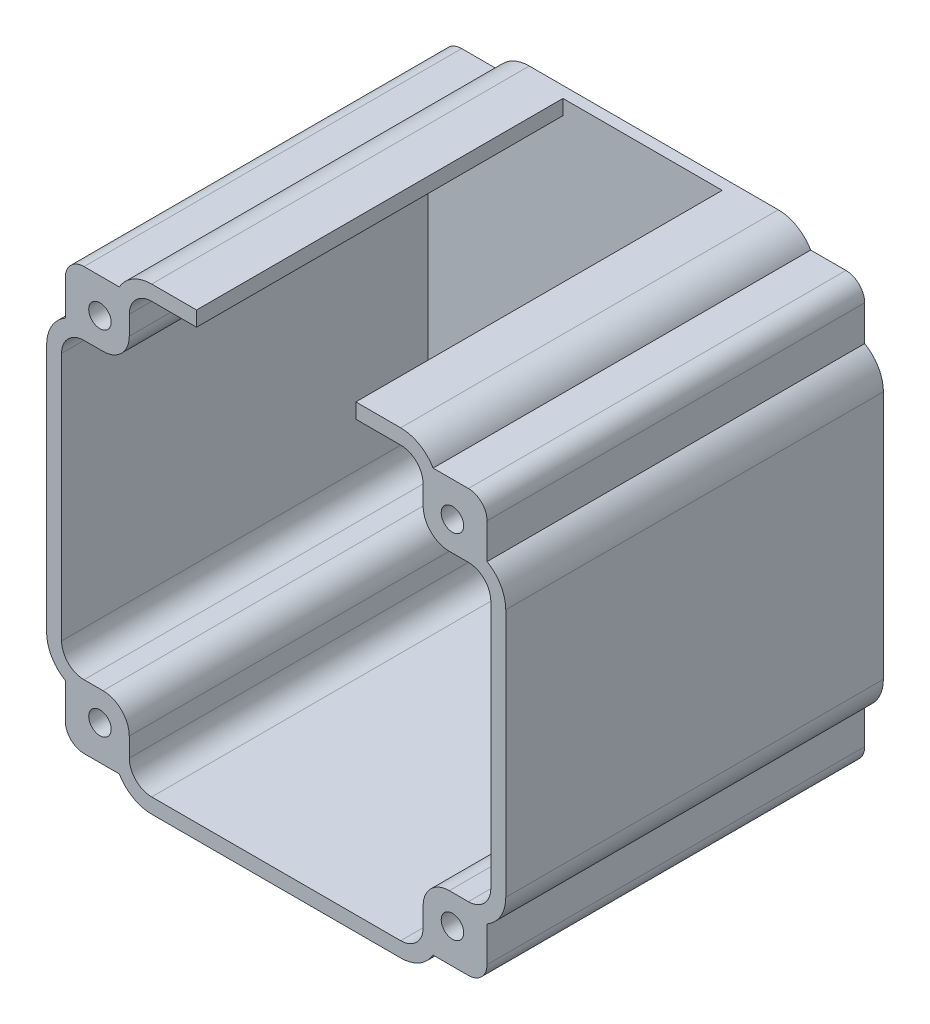
SolidWorks part; units mm, degrees
ref_plane "Front Plane" through (0, 0, 0) normal (0, 0, 1) x (1, 0, 0)
ref_plane "Top Plane" through (0, 0, 0) normal (0, 1, 0) x (1, 0, 0)
ref_plane "Right Plane" through (0, 0, 0) normal (1, 0, 0) x (0, 0, -1)
sketch "Sketch1" plane through (0, 0, -54) normal (0, 0, -1) x (-1, 0, 0)
  line L0 (-25.7, -19.65) -> (-23.15, -19.65)
  line L1 (-19.65, -23.15) -> (-19.65, -25.7)
  line L2 (-16.65, -28.7) -> (16.65, -28.7)
  line L3 (19.65, -25.7) -> (19.65, -23.15)
  line L4 (23.15, -19.65) -> (25.7, -19.65)
  line L5 (28.7, -16.65) -> (28.7, 16.65)
  line L6 (25.7, 19.65) -> (23.15, 19.65)
  line L7 (19.65, 23.15) -> (19.65, 25.7)
  line L8 (16.65, 28.7) -> (10.65, 28.7)
  line L9 (-19.65, 25.7) -> (-19.65, 23.15)
  line L10 (-23.15, 19.65) -> (-25.7, 19.65)
  line L11 (-28.7, 16.65) -> (-28.7, -16.65)
  line L12 (-25.7, -18.65) -> (-23.15, -18.65)
  line L13 (-18.65, -23.15) -> (-18.65, -25.7)
  line L14 (-16.65, -27.7) -> (16.65, -27.7)
  line L15 (18.65, -25.7) -> (18.65, -23.15)
  line L16 (23.15, -18.65) -> (25.7, -18.65)
  line L17 (27.7, -16.65) -> (27.7, 16.65)
  line L18 (25.7, 18.65) -> (23.15, 18.65)
  line L19 (18.65, 23.15) -> (18.65, 25.7)
  line L20 (16.65, 27.7) -> (-16.65, 27.7)
  line L21 (-18.65, 25.7) -> (-18.65, 23.15)
  line L22 (-23.15, 18.65) -> (-25.7, 18.65)
  line L23 (-27.7, 16.65) -> (-27.7, -16.65)
  line L24 (-25.7, -18.65) -> (-23.15, -18.65) construction
  line L25 (-18.65, -23.15) -> (-18.65, -25.7) construction
  line L26 (-16.65, -27.7) -> (16.65, -27.7) construction
  line L27 (18.65, -25.7) -> (18.65, -23.15) construction
  line L28 (23.15, -18.65) -> (25.7, -18.65) construction
  line L29 (27.7, -16.65) -> (27.7, 16.65) construction
  line L30 (25.7, 18.65) -> (23.15, 18.65) construction
  line L31 (18.65, 23.15) -> (18.65, 25.7) construction
  line L32 (16.65, 27.7) -> (-16.65, 27.7) construction
  line L33 (-18.65, 25.7) -> (-18.65, 23.15) construction
  line L34 (-23.15, 18.65) -> (-25.7, 18.65) construction
  line L35 (-27.7, 16.65) -> (-27.7, -16.65) construction
  line L36 (-25.7, -21.65) -> (-23.15, -21.65)
  line L37 (-21.65, -23.15) -> (-21.65, -25.7)
  line L38 (-16.65, -30.7) -> (16.65, -30.7)
  line L39 (21.65, -25.7) -> (21.65, -23.15)
  line L40 (23.15, -21.65) -> (25.7, -21.65)
  line L41 (30.7, -16.65) -> (30.7, 16.65)
  line L42 (25.7, 21.65) -> (23.15, 21.65)
  line L43 (21.65, 23.15) -> (21.65, 25.7)
  line L44 (16.65, 30.7) -> (10.65, 30.7)
  line L45 (-21.65, 25.7) -> (-21.65, 23.15)
  line L46 (-23.15, 21.65) -> (-25.7, 21.65)
  line L47 (-30.7, 16.65) -> (-30.7, -16.65)
  line L48 (-10.65, 30.7) -> (-10.65, 28.7)
  line L49 (10.65, 30.7) -> (10.65, 28.7)
  line L50 (-10.65, 30.7) -> (-16.65, 30.7)
  line L51 (16.65, 30.7) -> (-16.65, 30.7) construction
  line L52 (-10.65, 28.7) -> (-16.65, 28.7)
  line L53 (16.65, 28.7) -> (-16.65, 28.7) construction
  arc A0 (-19.65, -23.15) -> (-23.15, -19.65) centre (-23.15, -23.15) ccw
  arc A1 (-19.65, -25.7) -> (-16.65, -28.7) centre (-16.65, -25.7) ccw
  arc A2 (16.65, -28.7) -> (19.65, -25.7) centre (16.65, -25.7) ccw
  arc A3 (23.15, -19.65) -> (19.65, -23.15) centre (23.15, -23.15) ccw
  arc A4 (25.7, -19.65) -> (28.7, -16.65) centre (25.7, -16.65) ccw
  arc A5 (28.7, 16.65) -> (25.7, 19.65) centre (25.7, 16.65) ccw
  arc A6 (19.65, 23.15) -> (23.15, 19.65) centre (23.15, 23.15) ccw
  arc A7 (19.65, 25.7) -> (16.65, 28.7) centre (16.65, 25.7) ccw
  arc A8 (-16.65, 28.7) -> (-19.65, 25.7) centre (-16.65, 25.7) ccw
  arc A9 (-23.15, 19.65) -> (-19.65, 23.15) centre (-23.15, 23.15) ccw
  arc A10 (-25.7, 19.65) -> (-28.7, 16.65) centre (-25.7, 16.65) ccw
  arc A11 (-28.7, -16.65) -> (-25.7, -19.65) centre (-25.7, -16.65) ccw
  arc A12 (-27.7, -16.65) -> (-25.7, -18.65) centre (-25.7, -16.65) ccw
  arc A13 (-18.65, -23.15) -> (-23.15, -18.65) centre (-23.15, -23.15) ccw
  arc A14 (-18.65, -25.7) -> (-16.65, -27.7) centre (-16.65, -25.7) ccw
  arc A15 (16.65, -27.7) -> (18.65, -25.7) centre (16.65, -25.7) ccw
  arc A16 (23.15, -18.65) -> (18.65, -23.15) centre (23.15, -23.15) ccw
  arc A17 (25.7, -18.65) -> (27.7, -16.65) centre (25.7, -16.65) ccw
  arc A18 (27.7, 16.65) -> (25.7, 18.65) centre (25.7, 16.65) ccw
  arc A19 (18.65, 23.15) -> (23.15, 18.65) centre (23.15, 23.15) ccw
  arc A20 (18.65, 25.7) -> (16.65, 27.7) centre (16.65, 25.7) ccw
  arc A21 (-16.65, 27.7) -> (-18.65, 25.7) centre (-16.65, 25.7) ccw
  arc A22 (-23.15, 18.65) -> (-18.65, 23.15) centre (-23.15, 23.15) ccw
  arc A23 (-25.7, 18.65) -> (-27.7, 16.65) centre (-25.7, 16.65) ccw
  arc A24 (-27.7, -16.65) -> (-25.7, -18.65) centre (-25.7, -16.65) ccw construction
  arc A25 (-18.65, -23.15) -> (-23.15, -18.65) centre (-23.15, -23.15) ccw construction
  arc A26 (-18.65, -25.7) -> (-16.65, -27.7) centre (-16.65, -25.7) ccw construction
  arc A27 (16.65, -27.7) -> (18.65, -25.7) centre (16.65, -25.7) ccw construction
  arc A28 (23.15, -18.65) -> (18.65, -23.15) centre (23.15, -23.15) ccw construction
  arc A29 (25.7, -18.65) -> (27.7, -16.65) centre (25.7, -16.65) ccw construction
  arc A30 (27.7, 16.65) -> (25.7, 18.65) centre (25.7, 16.65) ccw construction
  arc A31 (18.65, 23.15) -> (23.15, 18.65) centre (23.15, 23.15) ccw construction
  arc A32 (18.65, 25.7) -> (16.65, 27.7) centre (16.65, 25.7) ccw construction
  arc A33 (-16.65, 27.7) -> (-18.65, 25.7) centre (-16.65, 25.7) ccw construction
  arc A34 (-23.15, 18.65) -> (-18.65, 23.15) centre (-23.15, 23.15) ccw construction
  arc A35 (-25.7, 18.65) -> (-27.7, 16.65) centre (-25.7, 16.65) ccw construction
  arc A36 (-21.65, -23.15) -> (-23.15, -21.65) centre (-23.15, -23.15) ccw
  arc A37 (-21.65, -25.7) -> (-16.65, -30.7) centre (-16.65, -25.7) ccw
  arc A38 (16.65, -30.7) -> (21.65, -25.7) centre (16.65, -25.7) ccw
  arc A39 (23.15, -21.65) -> (21.65, -23.15) centre (23.15, -23.15) ccw
  arc A40 (25.7, -21.65) -> (30.7, -16.65) centre (25.7, -16.65) ccw
  arc A41 (30.7, 16.65) -> (25.7, 21.65) centre (25.7, 16.65) ccw
  arc A42 (21.65, 23.15) -> (23.15, 21.65) centre (23.15, 23.15) ccw
  arc A43 (21.65, 25.7) -> (16.65, 30.7) centre (16.65, 25.7) ccw
  arc A44 (-16.65, 30.7) -> (-21.65, 25.7) centre (-16.65, 25.7) ccw
  arc A45 (-23.15, 21.65) -> (-21.65, 23.15) centre (-23.15, 23.15) ccw
  arc A46 (-25.7, 21.65) -> (-30.7, 16.65) centre (-25.7, 16.65) ccw
  arc A47 (-30.7, -16.65) -> (-25.7, -21.65) centre (-25.7, -16.65) ccw
  dimension "D4" = 6
  dimension "D5" = 6
  dimension "D1" = 0
  dimension "D2" = 1
  dimension "D3" = 2
extrude "Boss-Extrude1" add sketch "Sketch1" against normal up to surface (49 mm away)
sketch "Sketch2" plane through (0, 0, -54) normal (0, 0, -1) x (-1, 0, 0)
  line L0 (-10.65, 30.7) -> (10.65, 30.7)
  line L12 (-25.7, -21.65) -> (-23.15, -21.65)
  line L13 (-21.65, -23.15) -> (-21.65, -25.7)
  line L14 (-16.65, -30.7) -> (16.65, -30.7)
  line L15 (21.65, -25.7) -> (21.65, -23.15)
  line L16 (23.15, -21.65) -> (25.7, -21.65)
  line L17 (30.7, -16.65) -> (30.7, 16.65)
  line L18 (25.7, 21.65) -> (23.15, 21.65)
  line L19 (21.65, 23.15) -> (21.65, 25.7)
  line L20 (16.65, 30.7) -> (10.65, 30.7)
  line L21 (-21.65, 25.7) -> (-21.65, 23.15)
  line L22 (-23.15, 21.65) -> (-25.7, 21.65)
  line L23 (-30.7, 16.65) -> (-30.7, -16.65)
  line L24 (-25.7, -21.65) -> (-23.15, -21.65)
  line L25 (-21.65, -23.15) -> (-21.65, -25.7)
  line L26 (-16.65, -30.7) -> (16.65, -30.7)
  line L27 (21.65, -25.7) -> (21.65, -23.15)
  line L28 (23.15, -21.65) -> (25.7, -21.65)
  line L29 (30.7, -16.65) -> (30.7, 16.65)
  line L30 (25.7, 21.65) -> (23.15, 21.65)
  line L31 (21.65, 23.15) -> (21.65, 25.7)
  line L32 (16.65, 30.7) -> (10.65, 30.7)
  line L33 (-21.65, 25.7) -> (-21.65, 23.15)
  line L34 (-23.15, 21.65) -> (-25.7, 21.65)
  line L35 (-30.7, 16.65) -> (-30.7, -16.65)
  line L52 (-28.7, -16.65) -> (-28.7, 16.65)
  line L54 (-25.7, 19.65) -> (-23.15, 19.65)
  line L56 (-19.65, 23.15) -> (-19.65, 25.7)
  line L58 (-16.65, 28.7) -> (-10.65, 28.7)
  line L60 (-10.65, 28.7) -> (-10.65, 30.7)
  line L62 (-10.65, 30.7) -> (-16.65, 30.7)
  line L63 (-10.65, 30.7) -> (-16.65, 30.7)
  line L64 (10.65, 30.7) -> (10.65, 28.7)
  line L66 (10.65, 28.7) -> (16.65, 28.7)
  line L68 (19.65, 25.7) -> (19.65, 23.15)
  line L70 (23.15, 19.65) -> (25.7, 19.65)
  line L72 (28.7, 16.65) -> (28.7, -16.65)
  line L74 (25.7, -19.65) -> (23.15, -19.65)
  line L76 (19.65, -23.15) -> (19.65, -25.7)
  line L78 (16.65, -28.7) -> (-16.65, -28.7)
  line L80 (-19.65, -25.7) -> (-19.65, -23.15)
  line L82 (-23.15, -19.65) -> (-25.7, -19.65)
  arc A12 (-30.7, -16.65) -> (-25.7, -21.65) centre (-25.7, -16.65) ccw
  arc A13 (-21.65, -23.15) -> (-23.15, -21.65) centre (-23.15, -23.15) ccw
  arc A14 (-21.65, -25.7) -> (-16.65, -30.7) centre (-16.65, -25.7) ccw
  arc A15 (16.65, -30.7) -> (21.65, -25.7) centre (16.65, -25.7) ccw
  arc A16 (23.15, -21.65) -> (21.65, -23.15) centre (23.15, -23.15) ccw
  arc A17 (25.7, -21.65) -> (30.7, -16.65) centre (25.7, -16.65) ccw
  arc A18 (30.7, 16.65) -> (25.7, 21.65) centre (25.7, 16.65) ccw
  arc A19 (21.65, 23.15) -> (23.15, 21.65) centre (23.15, 23.15) ccw
  arc A20 (21.65, 25.7) -> (16.65, 30.7) centre (16.65, 25.7) ccw
  arc A21 (-16.65, 30.7) -> (-21.65, 25.7) centre (-16.65, 25.7) ccw
  arc A22 (-23.15, 21.65) -> (-21.65, 23.15) centre (-23.15, 23.15) ccw
  arc A23 (-25.7, 21.65) -> (-30.7, 16.65) centre (-25.7, 16.65) ccw
  arc A24 (-30.7, -16.65) -> (-25.7, -21.65) centre (-25.7, -16.65) ccw
  arc A25 (-21.65, -23.15) -> (-23.15, -21.65) centre (-23.15, -23.15) ccw
  arc A26 (-21.65, -25.7) -> (-16.65, -30.7) centre (-16.65, -25.7) ccw
  arc A27 (16.65, -30.7) -> (21.65, -25.7) centre (16.65, -25.7) ccw
  arc A28 (23.15, -21.65) -> (21.65, -23.15) centre (23.15, -23.15) ccw
  arc A29 (25.7, -21.65) -> (30.7, -16.65) centre (25.7, -16.65) ccw
  arc A30 (30.7, 16.65) -> (25.7, 21.65) centre (25.7, 16.65) ccw
  arc A31 (21.65, 23.15) -> (23.15, 21.65) centre (23.15, 23.15) ccw
  arc A32 (21.65, 25.7) -> (16.65, 30.7) centre (16.65, 25.7) ccw
  arc A33 (-16.65, 30.7) -> (-21.65, 25.7) centre (-16.65, 25.7) ccw
  arc A34 (-23.15, 21.65) -> (-21.65, 23.15) centre (-23.15, 23.15) ccw
  arc A35 (-25.7, 21.65) -> (-30.7, 16.65) centre (-25.7, 16.65) ccw
  arc A48 (-28.7, -16.65) -> (-25.7, -19.65) centre (-25.7, -16.65) ccw
  arc A50 (-25.7, 19.65) -> (-28.7, 16.65) centre (-25.7, 16.65) ccw
  arc A52 (-23.15, 19.65) -> (-19.65, 23.15) centre (-23.15, 23.15) ccw
  arc A54 (-16.65, 28.7) -> (-19.65, 25.7) centre (-16.65, 25.7) ccw
  arc A56 (19.65, 25.7) -> (16.65, 28.7) centre (16.65, 25.7) ccw
  arc A58 (19.65, 23.15) -> (23.15, 19.65) centre (23.15, 23.15) ccw
  arc A60 (28.7, 16.65) -> (25.7, 19.65) centre (25.7, 16.65) ccw
  arc A62 (25.7, -19.65) -> (28.7, -16.65) centre (25.7, -16.65) ccw
  arc A64 (23.15, -19.65) -> (19.65, -23.15) centre (23.15, -23.15) ccw
  arc A66 (16.65, -28.7) -> (19.65, -25.7) centre (16.65, -25.7) ccw
  arc A68 (-19.65, -25.7) -> (-16.65, -28.7) centre (-16.65, -25.7) ccw
  arc A70 (-19.65, -23.15) -> (-23.15, -19.65) centre (-23.15, -23.15) ccw
  dimension "D1" = 0
extrude "Boss-Extrude2" add sketch "Sketch2" along normal blind 1.5
sketch "Sketch3" plane through (0, 0, -55.5) normal (0, 0, -1) x (-1, 0, 0)
  line L0 (-21.65, 25.7) -> (-21.65, 23.15) construction
  line L1 (-25.7, 28.2) -> (-20.9801, 28.2) construction
  line L2 (-28.2, 20.9801) -> (-28.2, 25.7) construction
  line L3 (-23.15, 21.65) -> (-25.7, 21.65) construction
  line L4 (21.65, 25.7) -> (21.65, 23.15)
  line L5 (25.7, 28.2) -> (20.9801, 28.2)
  line L6 (28.2, 20.9801) -> (28.2, 25.7)
  line L7 (23.15, 21.65) -> (25.7, 21.65)
  line L8 (21.65, 25.7) -> (21.65, 23.15)
  line L9 (25.7, 28.2) -> (20.9801, 28.2)
  line L10 (28.2, 20.9801) -> (28.2, 25.7)
  line L11 (23.15, 21.65) -> (25.7, 21.65)
  line L12 (-23.15, -21.65) -> (-25.7, -21.65)
  line L13 (-21.65, -25.7) -> (-21.65, -23.15)
  line L14 (-25.7, -28.2) -> (-20.9801, -28.2)
  line L15 (-28.2, -20.9801) -> (-28.2, -25.7)
  line L16 (-23.15, -21.65) -> (-25.7, -21.65)
  line L17 (-21.65, -25.7) -> (-21.65, -23.15)
  line L18 (-25.7, -28.2) -> (-20.9801, -28.2)
  line L19 (-28.2, -20.9801) -> (-28.2, -25.7)
  line L20 (25.7, -21.65) -> (23.15, -21.65)
  line L21 (21.65, -23.15) -> (21.65, -25.7)
  line L22 (20.9801, -28.2) -> (25.7, -28.2)
  line L23 (28.2, -25.7) -> (28.2, -20.9801)
  line L24 (25.7, -21.65) -> (23.15, -21.65)
  line L25 (21.65, -23.15) -> (21.65, -25.7)
  line L26 (20.9801, -28.2) -> (25.7, -28.2)
  line L27 (28.2, -25.7) -> (28.2, -20.9801)
  line L28 (-21.65, 25.7) -> (-21.65, 23.15)
  line L29 (-25.7, 28.2) -> (-20.9801, 28.2)
  line L30 (-28.2, 20.9801) -> (-28.2, 25.7)
  line L31 (-23.15, 21.65) -> (-25.7, 21.65)
  arc A0 (-20.9801, 28.2) -> (-21.65, 25.7) centre (-16.65, 25.7) ccw construction
  arc A1 (-25.7, 28.2) -> (-28.2, 25.7) centre (-25.7, 25.7) ccw construction
  arc A2 (-25.7, 21.65) -> (-28.2, 20.9801) centre (-25.7, 16.65) ccw construction
  arc A3 (-20.9801, 28.2) -> (-21.65, 25.7) centre (-16.65, 25.7) ccw
  arc A4 (21.65, 25.7) -> (20.9801, 28.2) centre (16.65, 25.7) ccw
  arc A5 (28.2, 25.7) -> (25.7, 28.2) centre (25.7, 25.7) ccw
  arc A6 (28.2, 20.9801) -> (25.7, 21.65) centre (25.7, 16.65) ccw
  arc A7 (21.65, 23.15) -> (23.15, 21.65) centre (23.15, 23.15) ccw
  arc A8 (21.65, 25.7) -> (20.9801, 28.2) centre (16.65, 25.7) ccw
  arc A9 (28.2, 25.7) -> (25.7, 28.2) centre (25.7, 25.7) ccw
  arc A10 (28.2, 20.9801) -> (25.7, 21.65) centre (25.7, 16.65) ccw
  arc A11 (21.65, 23.15) -> (23.15, 21.65) centre (23.15, 23.15) ccw
  arc A12 (-21.65, -23.15) -> (-23.15, -21.65) centre (-23.15, -23.15) ccw
  arc A13 (-21.65, -25.7) -> (-20.9801, -28.2) centre (-16.65, -25.7) ccw
  arc A14 (-28.2, -25.7) -> (-25.7, -28.2) centre (-25.7, -25.7) ccw
  arc A15 (-28.2, -20.9801) -> (-25.7, -21.65) centre (-25.7, -16.65) ccw
  arc A16 (-21.65, -23.15) -> (-23.15, -21.65) centre (-23.15, -23.15) ccw
  arc A17 (-21.65, -25.7) -> (-20.9801, -28.2) centre (-16.65, -25.7) ccw
  arc A18 (-28.2, -25.7) -> (-25.7, -28.2) centre (-25.7, -25.7) ccw
  arc A19 (-28.2, -20.9801) -> (-25.7, -21.65) centre (-25.7, -16.65) ccw
  arc A20 (23.15, -21.65) -> (21.65, -23.15) centre (23.15, -23.15) ccw
  arc A21 (20.9801, -28.2) -> (21.65, -25.7) centre (16.65, -25.7) ccw
  arc A22 (25.7, -28.2) -> (28.2, -25.7) centre (25.7, -25.7) ccw
  arc A23 (25.7, -21.65) -> (28.2, -20.9801) centre (25.7, -16.65) ccw
  arc A24 (23.15, -21.65) -> (21.65, -23.15) centre (23.15, -23.15) ccw
  arc A25 (20.9801, -28.2) -> (21.65, -25.7) centre (16.65, -25.7) ccw
  arc A26 (25.7, -28.2) -> (28.2, -25.7) centre (25.7, -25.7) ccw
  arc A27 (25.7, -21.65) -> (28.2, -20.9801) centre (25.7, -16.65) ccw
  arc A28 (-25.7, 28.2) -> (-28.2, 25.7) centre (-25.7, 25.7) ccw
  arc A29 (-25.7, 21.65) -> (-28.2, 20.9801) centre (-25.7, 16.65) ccw
  point P47 (0, 0)
  arc M25 (-30.7, -16.65) -> (-25.7, -21.65) centre (-25.7, -16.65) ccw
  line M26 (-25.7, -21.65) -> (-23.15, -21.65)
  arc M27 (-23.15, -21.65) -> (-21.65, -23.15) centre (-23.15, -23.15) cw
  line M28 (-21.65, -23.15) -> (-21.65, -25.7)
  arc M29 (-21.65, -25.7) -> (-16.65, -30.7) centre (-16.65, -25.7) ccw
  arc M31 (16.65, -30.7) -> (21.65, -25.7) centre (16.65, -25.7) ccw
  line M32 (21.65, -25.7) -> (21.65, -23.15)
  arc M33 (21.65, -23.15) -> (23.15, -21.65) centre (23.15, -23.15) cw
  line M34 (23.15, -21.65) -> (25.7, -21.65)
  arc M35 (25.7, -21.65) -> (30.7, -16.65) centre (25.7, -16.65) ccw
  arc M37 (30.7, 16.65) -> (25.7, 21.65) centre (25.7, 16.65) ccw
  line M38 (25.7, 21.65) -> (23.15, 21.65)
  arc M39 (23.15, 21.65) -> (21.65, 23.15) centre (23.15, 23.15) cw
  line M40 (21.65, 23.15) -> (21.65, 25.7)
  arc M41 (21.65, 25.7) -> (16.65, 30.7) centre (16.65, 25.7) ccw
  arc M43 (-16.65, 30.7) -> (-21.65, 25.7) centre (-16.65, 25.7) ccw
  line M44 (-21.65, 25.7) -> (-21.65, 23.15)
  arc M45 (-21.65, 23.15) -> (-23.15, 21.65) centre (-23.15, 23.15) cw
  line M46 (-23.15, 21.65) -> (-25.7, 21.65)
  arc M47 (-25.7, 21.65) -> (-30.7, 16.65) centre (-25.7, 16.65) ccw
  dimension "D1" = 0
  dimension "D2" = 0
  dimension "D3" = 0
extrude "Boss-Extrude3" add sketch "Sketch3" against normal up to surface (50.5 mm away) contours L29 A28 L30 M47 M46 M45 M44 M43 | L10 A9 L9 M41 M40 M39 M38 M37 | L19 A18 L18 M29 M28 M27 M26 M25 | L26 A26 L27 M35 M34 M33 M32 M31 region at (-24.8618, 24.8618, -55.5) region at (24.8618, -24.8618, -55.5) region at (-24.8618, -24.8618, -55.5) region at (24.8618, 24.8618, -55.5)
sketch "Sketch4" plane through (0, 0, -5) normal (0, 0, 1) x (1, 0, 0)
  circle A0 centre (-23.57, 23.57) radius 1.5
  circle A1 centre (23.57, 23.57) radius 1.5
  circle A2 centre (-23.57, -23.57) radius 1.5
  circle A3 centre (23.57, -23.57) radius 1.5
  dimension "D1" = 3
extrude "Cut-Extrude1" cut sketch "Sketch4" against normal blind 10
